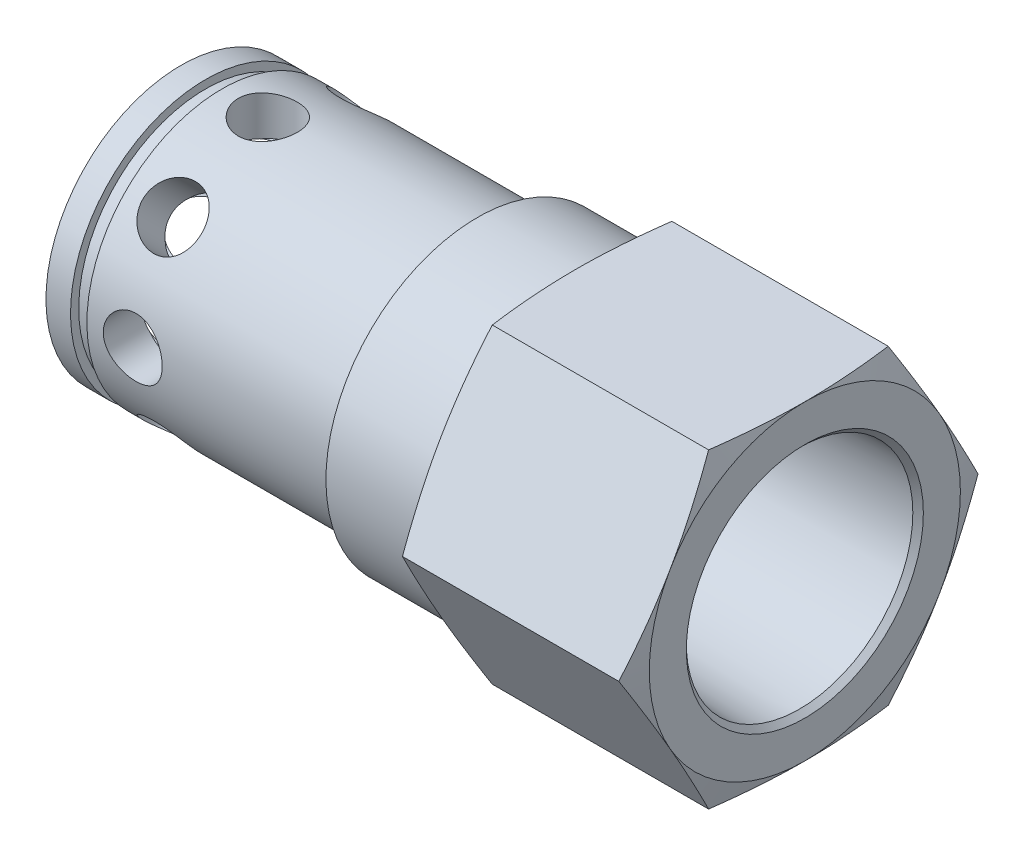
SolidWorks part; units mm, degrees
material "AISI 316 Annealed Stainless Steel Bar (SS)"
ref_plane "Front Plane" through (0, 0, 0) normal (0, 0, 1) x (1, 0, 0)
ref_plane "Top Plane" through (0, 0, 0) normal (0, 1, 0) x (1, 0, 0)
ref_plane "Right Plane" through (0, 0, 0) normal (1, 0, 0) x (0, 0, -1)
sketch "Sketch1" plane through (0, 0, 0) normal (1, 0, 0) x (0, 0, -1)
  line L1 (10.9697, 0) -> (5.4848, 9.5)
  line L2 (5.4848, 9.5) -> (-5.4848, 9.5)
  line L3 (-5.4848, 9.5) -> (-10.9697, 0)
  line L4 (-10.9697, 0) -> (-5.4848, -9.5)
  line L5 (-5.4848, -9.5) -> (5.4848, -9.5)
  line L6 (5.4848, -9.5) -> (10.9697, 0)
  circle A0 centre (0, 0) radius 9.5 construction
  circle A1 centre (0, 0) radius 3
  dimension "D2" = 6
  dimension "D1" = 19
extrude "Boss-Extrude1" add sketch "Sketch1" along normal blind 38.1
sketch "Sketch2" plane through (0, 0, 0) normal (0, 0, 1) x (1, 0, 0)
  line L0 (0, 0) -> (38.1, 0) construction
  line L1 (38.1, 0) -> (0, 0) construction
  line L2 (38.1, 0) -> (38.1, -9.5) construction
  line L3 (38.1, 9.5) -> (0, 9.5) construction
  line L4 (24.1, 9.5) -> (24.1, 9.25)
  line L5 (24.1, 9.25) -> (18.1, 9.25)
  line L6 (18.1, 9.25) -> (18.1, 8.25)
  line L7 (18.1, 8.25) -> (2.5, 8.25)
  line L8 (0, 9.5) -> (0, 0) construction
  line L9 (1.5, 8.25) -> (0, 8.25)
  line L10 (24.1, 9.5) -> (25.0378, 13)
  line L11 (1.5, 8.25) -> (1.5, 7.75)
  line L12 (1.5, 7.75) -> (2.5, 7.75)
  line L13 (2.5, 8.25) -> (2.5, 7.75)
  line L14 (25.0378, 13) -> (0, 13)
  line L15 (0, 13) -> (0, 8.25)
  line L16 (38.1, 9.5) -> (38.1, 13)
  line L17 (38.1, 13) -> (37.1622, 13)
  line L18 (37.1622, 13) -> (38.1, 9.5)
  dimension "D1" = 8.25
  dimension "D2" = 7.75
  dimension "D3" = 1.5
  dimension "D4" = 2.5
  dimension "D5" = 9.25
  dimension "D6" = 24.1
  dimension "D7" = 6
  dimension "D8" = 15
  dimension "D9" = 13
  dimension "D10" = 15
revolve "Cut-Revolve1" cut sketch "Sketch2" angle 360 about L0
sketch "Sketch3" plane through (0, 0, 0) normal (0, 0, 1) x (1, 0, 0)
  line L0 (0, 5.85) -> (9.9, 5.85)
  line L1 (0, 8.25) -> (0, -8.25) construction
  line L2 (9.9, 5.85) -> (10.95, 4.8)
  line L3 (10.95, 4.8) -> (13, 4.8)
  line L4 (13, 4.8) -> (13, 6.25)
  line L5 (13, 6.25) -> (15.5, 6.25)
  line L6 (15.5, 6.25) -> (15.5, 4.8)
  line L7 (15.5, 4.8) -> (21.4, 4.8)
  line L8 (21.4, 4.8) -> (21.4, 0)
  line L9 (0, 0) -> (21.4, 0)
  line L10 (0, 0) -> (0, 5.85)
  dimension "D1" = 9.9
  dimension "D2" = 21.4
  dimension "D3" = 13
  dimension "D4" = 2.5
  dimension "D5" = 4.8
  dimension "D6" = 5.85
  dimension "D7" = 45
  dimension "D8" = 6.25
revolve "Cut-Revolve2" cut sketch "Sketch3" angle 360 about L9
fillet "Fillet1" radius 0.2 2 edges at (15.5, 0, 6.25) (13, 0, 6.25)
hole_wizard "1/4 NPT Tapped Hole1" positions "Sketch5" profile "Sketch4" size "1/4" standard "ANSI Inch"
sketch "Sketch5" plane through (38.1, 0, 0) normal (1, 0, 0) x (0, 0, -1)
  point P0 (0, 0)
sketch "Sketch4" plane through (38.1, 0, 0) normal (0, 1, 0) x (0, 0, -1)
  line L0 (0, 0) -> (0, 14.2)
  line L1 (5.5626, 14.2) -> (0, 14.2)
  line L2 (-5.5626, 14.2) -> (0, 14.2) construction
  line L3 (5.5626, 14.2) -> (5.5626, 12)
  line L4 (5.5626, 12) -> (6.5676, 12)
  line L5 (6.5676, 12) -> (6.9173, 0.3217)
  line L6 (6.9173, 0.3217) -> (7.239, 0)
  line L7 (7.239, 0) -> (0, 0)
  line L8 (0, -6.35) -> (0, 107.95) construction
  line L9 (-6.9173, 0.3217) -> (-7.239, 0) construction
  line L11 (-5.5626, 12) -> (-6.5676, 12) construction
  line L12 (-6.5676, 12) -> (-6.9173, 0.3217) construction
  dimension "Tap Drill Dia." = 11.1252
  dimension "Tap Drill Depth" = 14.2
  dimension "Thread Dia." = 13.8345
  dimension "Thread Angle" = 3.43
  dimension "Thread Depth" = 12
  dimension "C'Sink Dia." = 14.478
  dimension "C'Sink Angle" = 90
  dimension "Drill Angle" = 180
ref_plane "Plane1" through (0, 0, 8.25) normal (0, 0, 1) x (1, 0, 0)
sketch "Sketch12" plane through (0, 0, 0) normal (0, 1, 0) x (1, 0, 0)
  line L0 (5.3, 8.25) -> (5.3, 5.6298)
  line L1 (18.1, 8.25) -> (2.5, 8.25) construction
  line L2 (5.3, 8.25) -> (7.1, 8.25)
  line L3 (7.1, 8.25) -> (7.1, 5.75)
  line L4 (7.1, 5.75) -> (6.9, 5.6298)
  line L5 (6.9, 5.6298) -> (5.3, 5.6298)
  line L6 (0, 8.25) -> (0, -8.25) construction
  dimension "D1" = 1.8
  dimension "D2" = 2.5
  dimension "D3" = 59
  dimension "D4" = 5.3
  dimension "D5" = 1.6
revolve "Cut-Revolve3" cut sketch "Sketch12" angle 360 about L0
pattern_circular "CirPattern1" count 8 over 360 about axis through (0, 0, 0) along (-1, 0, 0) of "Cut-Revolve3"
